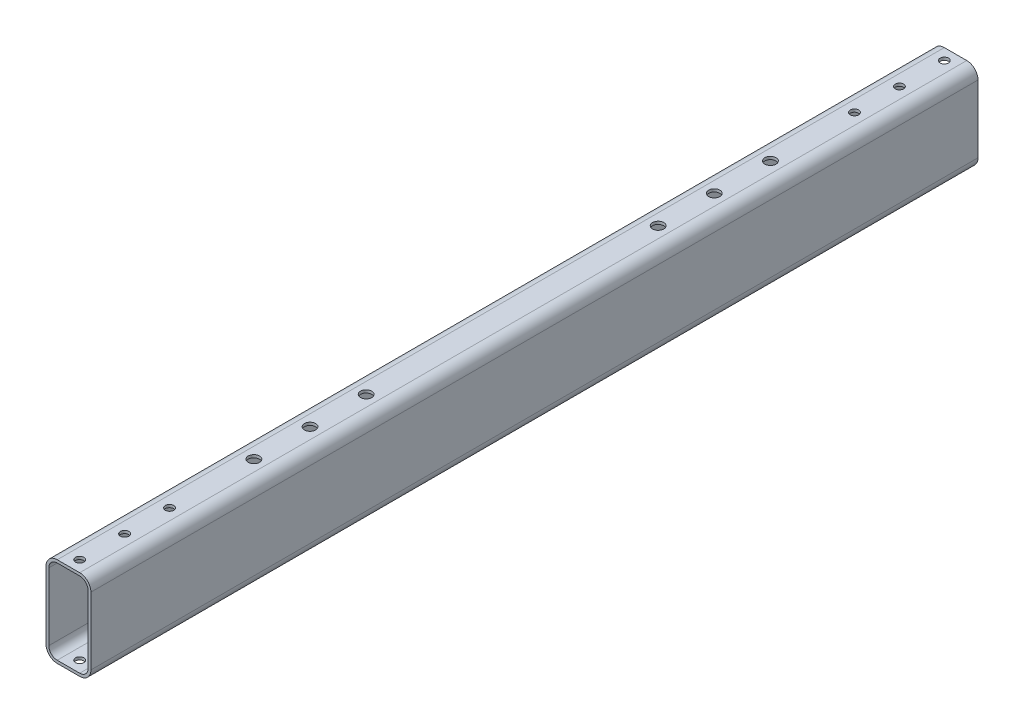
SolidWorks part; units mm, degrees
material "6061-T6 (SS)"
ref_plane "Front Plane" through (0, 0, 0) normal (0, 0, 1) x (1, 0, 0)
ref_plane "Top Plane" through (0, 0, 0) normal (0, 1, 0) x (1, 0, 0)
ref_plane "Right Plane" through (0, 0, 0) normal (1, 0, 0) x (0, 0, -1)
sketch "Sketch1" plane through (0, 0, 0) normal (0, 0, 1) x (1, 0, 0)
  line L1 (-6.35, -25.4) -> (6.35, -25.4)
  line L2 (-12.7, -19.05) -> (-12.7, 19.05)
  line L3 (-6.35, 25.4) -> (6.35, 25.4)
  line L4 (12.7, -19.05) -> (12.7, 19.05)
  line L5 (-12.7, -25.4) -> (12.7, 25.4) construction
  line L6 (-12.7, 25.4) -> (12.7, -25.4) construction
  arc A0 (-12.7, -19.05) -> (-6.35, -25.4) centre (-6.35, -19.05) ccw
  arc A1 (6.35, -25.4) -> (12.7, -19.05) centre (6.35, -19.05) ccw
  arc A2 (6.35, 25.4) -> (12.7, 19.05) centre (6.35, 19.05) cw
  arc A3 (-12.7, 19.05) -> (-6.35, 25.4) centre (-6.35, 19.05) cw
  point P0 (0, 0)
  dimension "D3" = 6.35
  dimension "D1" = 50.8
  dimension "D2" = 25.4
extrude "Extrude-Thin1" add sketch "Sketch1" along normal blind 501.65 thin thin type one direction reverse wall 1.5875
hole_wizard "3/16 (0.1875) Diameter Hole1" positions "3DSketch1" profile "Sketch3" hole size "3/16" standard "ANSI Inch" end condition through all
sketch3d "3DSketch1"
  line L1 (6.35, 25.4, 0) -> (-6.35, 25.4, 0) construction
  line L6 (0, 25.4, 501.65) -> (0, 25.4, 0) construction
  line L7 (6.35, 25.4, 501.65) -> (-6.35, 25.4, 501.65) construction
  point P57 (0, 25.4, 6.35)
  point P59 (0, 25.4, 31.75)
  point P61 (0, 25.4, 57.15)
  point P63 (0, 25.4, 469.9)
  point P65 (0, 25.4, 444.5)
  point P67 (0, 25.4, 495.3)
  dimension "D1" = 25.4
  dimension "D2" = 25.4
  dimension "D3" = 6.35
  dimension "D4" = 25.4
  dimension "D5" = 25.4
  dimension "D6" = 6.35
sketch "Sketch3" plane through (0, 25.4, 495.3) normal (1, 0, 0) x (0, 0, 1)
  line L0 (0, 0) -> (0, 50.8)
  line L1 (0, 50.8) -> (2.3812, 50.8)
  line L2 (2.3812, 50.8) -> (2.3812, 0)
  line L5 (2.3812, 0) -> (0, 0)
  line L11 (0, -6.35) -> (0, 107.95) construction
  dimension "Thru Hole Dia." = 4.7625
  dimension "Thru Hole Depth" = 50.8
hole_wizard "3/16 (0.195) Diameter Hole1" positions "Sketch4" profile "Sketch5" hole size "3/16" standard "ANSI Inch" end condition up to next
sketch "Sketch4" plane through (0, -25.4, 0) normal (0, -1, 0) x (-1, 0, 0)
  point P74 (-3.175, -85.725)
  point P78 (3.175, -111.125)
  point P81 (-3.175, -136.525)
  point P84 (3.175, -161.925)
  point P87 (-3.175, -187.325)
  point P90 (3.175, -212.725)
  point P93 (-3.175, -238.125)
  point P96 (3.175, -263.525)
  point P99 (-3.175, -288.925)
  point P102 (3.175, -314.325)
  point P105 (-3.175, -339.725)
  point P108 (3.175, -365.125)
  point P111 (3.175, -415.925)
  point P114 (-3.175, -390.525)
sketch "Sketch5" plane through (3.175, -25.4, 85.725) normal (1, 0, 0) x (0, 0, -1)
  line L0 (0, 0) -> (0, 1.5875)
  line L1 (0, 1.5875) -> (2.4765, 1.5875)
  line L2 (2.4765, 1.5875) -> (2.4765, 0)
  line L5 (2.4765, 0) -> (0, 0)
  line L11 (0, -6.35) -> (0, 107.95) construction
  dimension "Thru Hole Dia." = 4.953
  dimension "Thru Hole Depth" = 1.5875
hole_wizard "1/4 (0.25) Diameter Hole1" positions "Sketch6" profile "Sketch7" hole size "1/4" standard "ANSI Inch"
sketch "Sketch6" plane through (0, 25.4, 0) normal (0, 1, 0) x (1, 0, 0)
  point P0 (0, -104.6752)
  point P3 (0, -136.4252)
  point P6 (0, -168.1752)
  point P9 (0, -396.8)
  point P12 (0, -365.05)
  point P15 (0, -333.3)
sketch "Sketch7" plane through (0, 25.4, 104.6752) normal (1, 0, 0) x (0, 0, 1)
  line L0 (0, 0) -> (0, 27.3077)
  line L1 (0, 27.3077) -> (3.175, 25.4)
  line L2 (3.175, 25.4) -> (3.175, 0)
  line L5 (3.175, 0) -> (0, 0)
  line L10 (0, 27.3077) -> (-3.175, 25.4) construction
  line L11 (0, -6.35) -> (0, 107.95) construction
  dimension "Hole Dia." = 6.35
  dimension "Hole Depth" = 25.4
  dimension "Drill Angle" = 118
